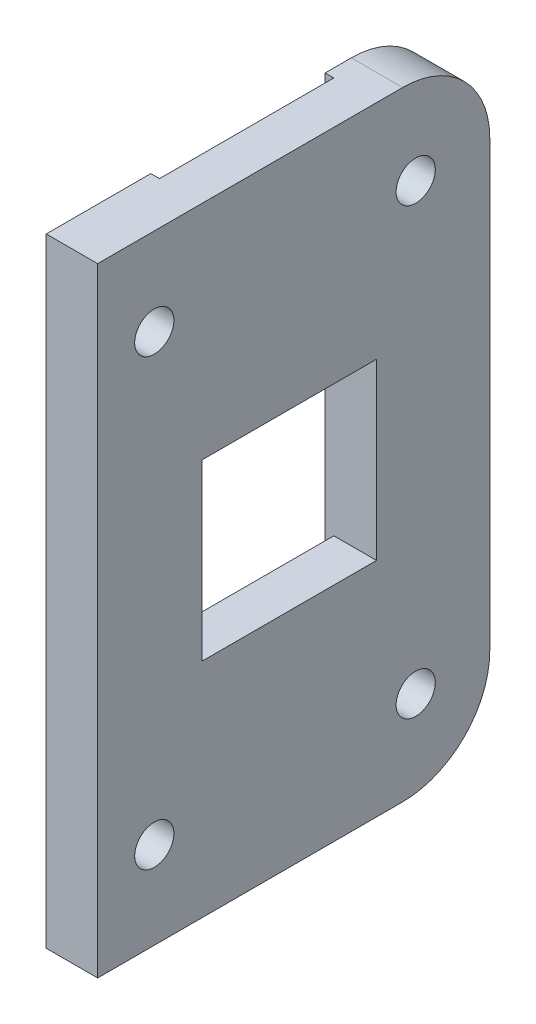
SolidWorks part; units mm, degrees
ref_plane "Front Plane" through (0, 0, 0) normal (0, 0, 1) x (1, 0, 0)
ref_plane "Top Plane" through (0, 0, 0) normal (0, 1, 0) x (1, 0, 0)
ref_plane "Right Plane" through (0, 0, 0) normal (1, 0, 0) x (0, 0, -1)
sketch "Sketch1" plane through (0, 0, 0) normal (0, 1, 0) x (1, 0, 0)
  line L0 (0, 24.8) -> (0, -20.2)
  line L4 (5.9, -20.2) -> (5.9, 24.8)
  line L5 (5.9, 24.8) -> (0, 24.8)
  line L6 (-5.9995, -20.2) -> (0.0005, -20.2) construction
  line L8 (0, -20.2) -> (5.9, -20.2)
extrude "Boss-Extrude1" add sketch "Sketch1" along normal blind 71
sketch "Sketch3" plane through (0, 0, 0) normal (0, -1, 0) x (1, 0, 0)
  line L0 (0, -24.8) -> (0, 20.2) construction
  line L1 (0, -11.8) -> (1, -11.8)
  line L2 (0, -11.8) -> (0, 8.2)
  line L3 (0, 8.2) -> (1, 8.2)
  line L4 (1, -11.8) -> (1, 8.2)
  line L5 (5.9, -24.8) -> (0, -24.8) construction
  dimension "D1" = 1
  dimension "D2" = 13
  dimension "D3" = 20
extrude "Cut-Extrude2" cut sketch "Sketch3" against normal up to next
fillet "Fillet1" radius 10 2 edges at (2.95, 0, -24.8) (2.95, 71, -24.8)
sketch "Sketch4" plane through (5.9, 0, 0) normal (1, 0, 0) x (0, 0, -1)
  circle A9 centre (-13.7, 61) radius 2.25 construction
  circle A10 centre (-13.7, 10) radius 2.25 construction
  circle A11 centre (16.3, 10) radius 2.25 construction
  circle A12 centre (16.3, 61) radius 2.25 construction
  circle A13 centre (-13.7, 61) radius 2.25
  circle A14 centre (-13.7, 10) radius 2.25
  circle A15 centre (16.3, 10) radius 2.25
  circle A16 centre (16.3, 61) radius 2.25
  point P2 (0, 0)
  point P5 (0, 0)
  point P10 (0, 0)
  point P11 (0, 0)
extrude "Cut-Extrude3" cut sketch "Sketch4" against normal up to next
sketch "Sketch5" plane through (5.9, 0, 0) normal (1, 0, 0) x (0, 0, -1)
  line L0 (11.8, 71) -> (11.8, 0) construction
  line L1 (11.8, 45.5) -> (-8.2, 45.5)
  line L2 (11.8, 45.5) -> (11.8, 25.5)
  line L3 (11.8, 25.5) -> (-8.2, 25.5)
  line L4 (-8.2, 45.5) -> (-8.2, 25.5)
  line L5 (-8.2, 71) -> (-8.2, 0) construction
  line L6 (24.8, 35.5) -> (-4.819, 35.5) construction
  line L7 (24.8, 61) -> (24.8, 10) construction
  point P10 (11.8, 35.5)
  dimension "D1" = 20
extrude "Cut-Extrude4" cut sketch "Sketch5" against normal up to next
